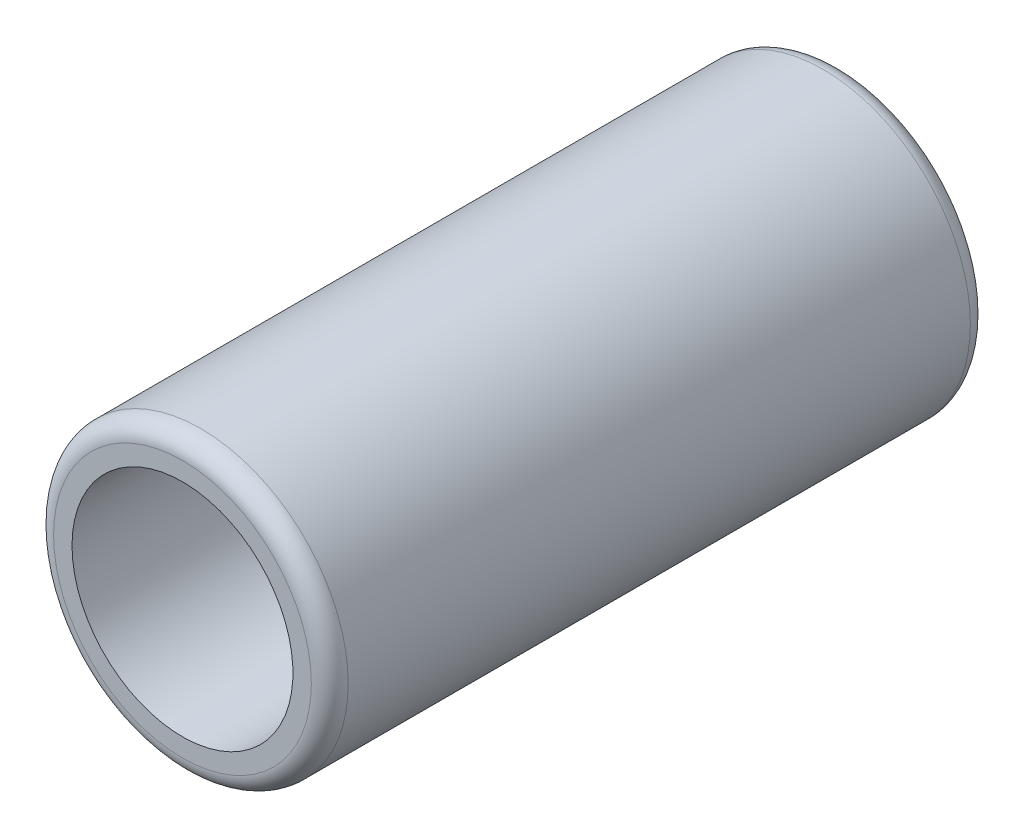
SolidWorks part; units mm, degrees
ref_plane "Спереди" through (0, 0, 0) normal (0, 0, 1) x (1, 0, 0)
ref_plane "Сверху" through (0, 0, 0) normal (0, 1, 0) x (1, 0, 0)
ref_plane "Справа" through (0, 0, 0) normal (1, 0, 0) x (0, 0, -1)
sketch "Sketch1" plane through (0, 0, 0) normal (0, 0, 1) x (1, 0, 0)
  circle A0 centre (0, 0) radius 4
  circle A1 centre (0, 0) radius 3
  dimension "D1" = 8
  dimension "D2" = 6
extrude "Boss-Extrude1" add sketch "Sketch1" along normal blind 17.9
fillet "Fillet1" radius 0.5 2 edges at (4, 0, 0) (4, 0, 17.9)
